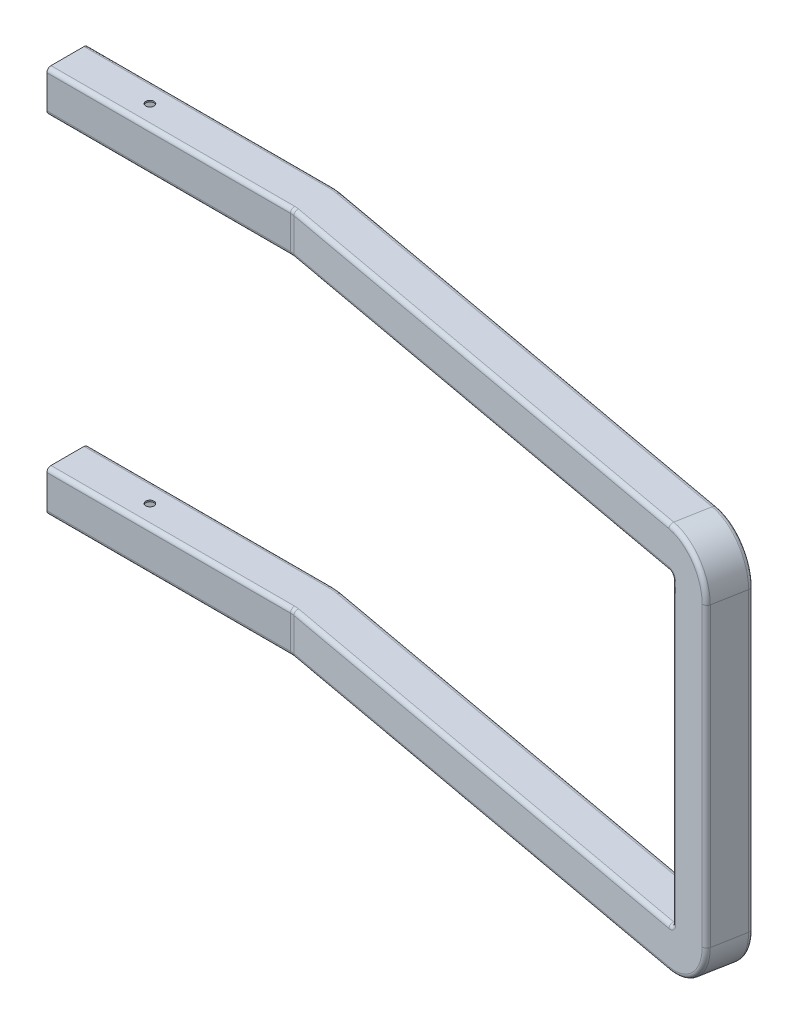
SolidWorks part; units mm, degrees
other "Markup1"
sketch "Sketch29" [suppressed] plane through (-50, 12.7, -12.7) normal (-0.6703, 0.7401, -0.0544) x (0.7356, 0.653, -0.1804)
sketch "Sketch30" [suppressed] plane through (-50, 20, -18.6944) normal (-0.6703, 0.7401, -0.0544) x (0.7356, 0.653, -0.1804)
sketch "Sketch34" [suppressed] plane through (-50, 20, -18.6944) normal (-0.6703, 0.7401, -0.0544) x (0.7356, 0.653, -0.1804)
sketch "Sketch35" [suppressed] plane through (-50, 30, -28.5496) normal (-0.6703, 0.7401, -0.0544) x (0.7356, 0.653, -0.1804)
sketch "Sketch36" [suppressed] plane through (-50, 30, -28.5496) normal (-0.6703, 0.7401, -0.0544) x (0.7356, 0.653, -0.1804)
sketch "Sketch37" plane through (-50, 30, -28.5496) normal (-0.6703, 0.7401, -0.0544) x (0.7356, 0.653, -0.1804)
material "5052-O"
ref_plane "Front Plane" through (0, 0, 0) normal (0, 0, 1) x (1, 0, 0)
ref_plane "Top Plane" through (0, 0, 0) normal (0, 1, 0) x (1, 0, 0)
ref_plane "Right Plane" through (0, 0, 0) normal (1, 0, 0) x (0, 0, -1)
sketch "Sketch2" plane through (0, 0, 0) normal (1, 0, 0) x (0, 0, -1)
  line L1 (-20, -25) -> (20, -25)
  line L2 (-25, -20) -> (-25, 20)
  line L3 (-20, 25) -> (20, 25)
  line L4 (25, -20) -> (25, 20)
  line L5 (-25, -25) -> (25, 25) construction
  line L6 (-25, 25) -> (25, -25) construction
  arc A0 (25, -20) -> (20, -25) centre (20, -20) cw
  arc A1 (-20, -25) -> (-25, -20) centre (-20, -20) cw
  arc A2 (-25, 20) -> (-20, 25) centre (-20, 20) cw
  arc A3 (20, 25) -> (25, 20) centre (20, 20) cw
  point P0 (0, 0)
  dimension "D3" = 5
  dimension "D1" = 50
  dimension "D2" = 50
sketch3d "3DSketch2"
  line L0 (0, 0, 0) -> (840.2912, 0, 0) construction
  line L1 (840.2912, 0, 0) -> (840.2912, -210, 0) construction
  line L2 (840.2912, -210, 0) -> (840.2912, -210, 107.5) construction
  line L3 (0, 0, 0) -> (245.4843, 0, 0)
  line L4 (254.4426, 0, 0.8091) -> (810.7767, 0, 102.125)
  line L5 (0, 0, 0) -> (-50, 0, 0)
  line L6 (0, 0, 0) -> (0, -210, 0) construction
  line L7 (840.2912, -210, 107.5) -> (840.2912, -210, 287.5) construction
  line L8 (840.2912, -210, 287.5) -> (-9.7834, -210, 287.5) construction
  line L9 (840.2912, -30, 107.5) -> (840.2912, -210, 107.5)
  arc A0 (254.4426, 0, 0.8091) -> (245.4843, 0, 0) centre (245.4843, 0, 50) ccw
  arc A1 (840.2912, -30, 107.5) -> (810.7767, 0, 102.125) centre (810.7767, -30, 102.125) ccw
  point P16 (250, 0, 0)
  point P17 (245.4843, 50, 50)
  point P20 (840.2912, 0, 107.5)
  point P21 (805.4017, -30, 131.6396)
  dimension "5" = 50
  dimension "D9" = 30
  dimension "D1" = 250
  dimension "D2" = 50
  dimension "D3" = 210
  dimension "D4" = 107.5
  dimension "D5" = 210
  dimension "D6" = 600
  dimension "D7" = 180
  dimension "D8" = 210
sweep "Sweep-Thin3" add profiles "Sketch2" path "3DSketch2" parameters "D1"=1.65
sketch "Sketch21" plane through (0, 0, 0) normal (0, 1, 0) x (1, 0, 0)
  line L0 (0, 0) -> (245.4843, 0) construction
  circle A0 centre (50, 0) radius 5
  dimension "D1" = 10
  dimension "D2" = 50
extrude "Cut-Extrude3" cut sketch "Sketch21" against normal through all both and the other way through all
sketch "Sketch22" [suppressed] plane through (0, 0, 0) normal (0, 0, 1) x (1, 0, 0)
ref_plane "Plane1" [suppressed] through (0, -210, 0) normal (0, 1, 0) x (1, 0, 0)
ref_plane "Plane2" through (0, -210, 0) normal (0, -1, 0) x (-1, 0, 0)
ref_plane "Plane3" through (0, -210, 0) normal (0, -1, 0) x (-1, 0, 0)
mirror "Mirror1" about plane through (0, -210, 0) normal (0, -1, 0) of "Cut-Extrude3", "Sweep-Thin3"
ref_plane "Plane4" [suppressed] through (2.91, 0, -15.9792) normal (-0.1792, 0, 0.9838) x (0.9838, 0, 0.1792)
sketch "Sketch23" [suppressed] plane through (2.91, 0, -15.9792) normal (-0.1792, 0, 0.9838) x (0.9838, 0, 0.1792)
  line L0 (874.5043, -30) -> (874.5043, -390) construction
  line L1 (874.5043, 30) -> (674.5043, 30)
  line L2 (874.5043, 30) -> (874.5043, -450)
  line L3 (874.5043, -450) -> (674.5043, -450)
  line L4 (674.5043, 30) -> (674.5043, -450)
  line L5 (868.2597, -30) -> (868.2597, -390) construction
  point P8 (868.2597, -210)
  point P9 (874.5043, -210)
  dimension "D1" = 480
  dimension "D2" = 200
extrude "Boss-Extrude1" [suppressed] add sketch "Sketch23" along normal blind 25.4
sketch "Sketch25" [suppressed] plane through (2.91, 0, -15.9792) normal (0.1792, 0, -0.9838) x (-0.9838, 0, -0.1792)
  line L0 (-674.5043, -22.305) -> (-674.5043, -397.695) construction
  line L1 (-816.5543, -174.3) -> (-732.4543, -174.3) construction
  line L2 (-816.5543, -174.3) -> (-816.5543, -245.7) construction
  line L3 (-816.5543, -245.7) -> (-732.4543, -245.7) construction
  line L4 (-732.4543, -174.3) -> (-732.4543, -245.7) construction
  line L5 (-816.5543, -174.3) -> (-732.4543, -245.7) construction
  line L6 (-816.5543, -245.7) -> (-732.4543, -174.3) construction
  line L7 (-874.5043, 30) -> (-674.5043, 30) construction
  line L8 (-729.1662, -177.588) -> (-735.7423, -171.012) construction
  line L9 (-732.525, -180.9468) -> (-739.1011, -174.3707)
  line L10 (-725.8075, -174.2293) -> (-732.3836, -167.6532)
  line L11 (-732.4543, -210) -> (-816.5543, -210) construction
  line L12 (-774.5043, -174.3) -> (-774.5043, -245.7) construction
  line L13 (-729.1662, -242.412) -> (-735.7423, -248.988) construction
  line L14 (-732.525, -239.0532) -> (-739.1011, -245.6293)
  line L15 (-725.8075, -245.7707) -> (-732.3836, -252.3468)
  line L16 (-819.8423, -242.412) -> (-813.2662, -248.988) construction
  line L17 (-816.4836, -239.0532) -> (-809.9075, -245.6293)
  line L18 (-823.2011, -245.7707) -> (-816.625, -252.3468)
  line L19 (-819.8423, -177.588) -> (-813.2662, -171.012) construction
  line L20 (-816.4836, -180.9468) -> (-809.9075, -174.3707)
  line L21 (-823.2011, -174.2293) -> (-816.625, -167.6532)
  arc A0 (-732.525, -180.9468) -> (-725.8075, -174.2293) centre (-729.1662, -177.588) ccw
  arc A1 (-732.3836, -167.6532) -> (-739.1011, -174.3707) centre (-735.7423, -171.012) ccw
  arc A2 (-732.525, -239.0532) -> (-725.8075, -245.7707) centre (-729.1662, -242.412) cw
  arc A3 (-732.3836, -252.3468) -> (-739.1011, -245.6293) centre (-735.7423, -248.988) cw
  arc A4 (-816.4836, -239.0532) -> (-823.2011, -245.7707) centre (-819.8423, -242.412) ccw
  arc A5 (-816.625, -252.3468) -> (-809.9075, -245.6293) centre (-813.2662, -248.988) ccw
  arc A6 (-816.4836, -180.9468) -> (-823.2011, -174.2293) centre (-819.8423, -177.588) cw
  arc A7 (-816.625, -167.6532) -> (-809.9075, -174.3707) centre (-813.2662, -171.012) cw
  point P0 (-774.5043, -210)
  point P7 (-674.5043, -210)
  point P10 (-774.5043, 30)
  point P13 (-732.4543, -174.3)
  point P24 (-732.4543, -245.7)
  point P31 (-816.5543, -245.7)
  point P38 (-816.5543, -174.3)
  dimension "D1" = 71.4
  dimension "D2" = 84.1
  dimension "D3" = 45
  dimension "D4" = 9.5
  dimension "D5" = 9.3
extrude "Cut-Extrude4" [suppressed] cut sketch "Sketch25" against normal through all
ref_plane "Plane7" [suppressed] through (661.9492, 30, 129.8584) normal (0, -1, 0) x (-1, 0, 0)
sketch "Sketch28" [suppressed] plane through (-1.6408, 0, 9.0097) normal (-0.1792, 0, 0.9838) x (0.9838, 0, 0.1792)
  line L0 (874.5043, 30) -> (674.5043, 30) construction
  line L1 (717.3543, -159.2) -> (831.6543, -159.2)
  line L2 (717.3543, -159.2) -> (717.3543, -260.8)
  line L3 (717.3543, -260.8) -> (831.6543, -260.8)
  line L4 (831.6543, -159.2) -> (831.6543, -260.8)
  line L5 (717.3543, -159.2) -> (831.6543, -260.8) construction
  line L6 (717.3543, -260.8) -> (831.6543, -159.2) construction
  line L7 (674.5043, 30) -> (674.5043, -450) construction
  point P0 (774.5043, -210)
  point P7 (774.5043, 30)
  point P10 (674.5043, -210)
  dimension "D1" = 101.6
  dimension "D2" = 114.3
fillet "Fillet1" [suppressed] radius 30
fillet "Fillet2" [suppressed] radius 0.9144 profile chamfer
ref_plane "Plane5" [suppressed] through (0, 0, 0) normal (-1, 0, 0) x (0, 0, 1)
ref_plane "EndOfTubePlane" [suppressed] through (140, 0, 0) normal (-1, 0, 0) x (0, 0, 1)
split line "Split Line1" [suppressed]
split line "Split Line2" [suppressed]
ref_plane "Plane8" [suppressed] through (806.7804, -391.4504, 124.0691) normal (0.9838, 0, 0.1792) x (0.1792, 0, -0.9838)
sketch "Sketch33" [suppressed] plane through (0, 0, 0) normal (0, 1, 0) x (1, 0, 0)
  line L0 (140, -28.5496) -> (245.4843, -28.5496) construction
  line L1 (249.3275, -28.8967) -> (665.6004, -104.7056) construction
  line L2 (-50, -28.5496) -> (140, -28.5496) construction
  arc A0 (140, -28.5496) -> (365.0664, -49.9743) centre (273.909, 185.2905) ccw
rib "Rib4" [suppressed] sketch "Sketch33" sketch "Sketch33" thickness 10 extrusion direction parallel to sketch draft on no parameters "D1"=10
chamfer "Chamfer1" [suppressed] distance 2.5 angle 45
mirror "Mirror2" [suppressed] about plane through (0, -210, 0) normal (0, -1, 0)
